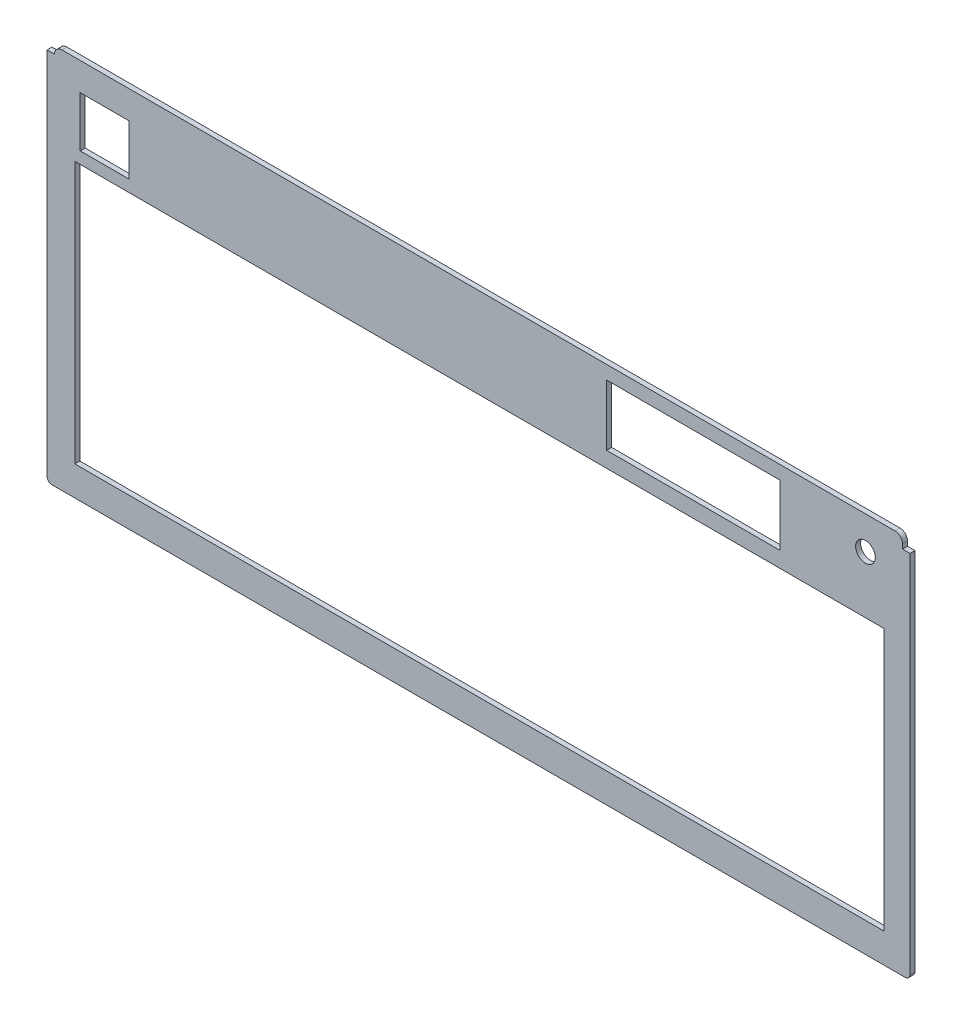
SolidWorks part; units mm, degrees
ref_plane "Front Plane" through (0, 0, 0) normal (0, 0, 1) x (1, 0, 0)
ref_plane "Top Plane" through (0, 0, 0) normal (0, 1, 0) x (1, 0, 0)
ref_plane "Right Plane" through (0, 0, 0) normal (1, 0, 0) x (0, 0, -1)
sketch "Sketch1" plane through (0, 0, 0) normal (0, 0, 1) x (1, 0, 0)
  line L0 (-65.3452, 80.1382) -> (268.63, 80.1382)
  line L6 (268.63, -69.8367) -> (-65.3452, -69.8367)
  line L7 (-68.3452, -66.8367) -> (-68.3452, 77.1382)
  line L10 (271.63, -66.8367) -> (271.63, 77.1382)
  line L12 (153.0356, 74.6937) -> (153.0356, 50.3137)
  line L13 (-58.0282, 68.9533) -> (-38.5345, 68.9533)
  line L14 (-58.0282, 68.9533) -> (-58.0282, 48.7377)
  line L15 (-58.0282, 48.7377) -> (-38.5345, 48.7377)
  line L16 (-38.5345, 68.9533) -> (-38.5345, 48.7377)
  line L17 (-60.1941, 44.0447) -> (264.3023, 44.0447)
  line L18 (-60.1941, 44.0447) -> (-60.1941, -61.0045)
  line L19 (-60.1941, -61.0045) -> (264.3023, -61.0045)
  line L20 (264.3023, 44.0447) -> (264.3023, -61.0045)
  line L25 (153.0356, 50.3137) -> (222.4656, 50.3137)
  line L26 (153.0356, 50.3137) -> (222.4656, 50.3137) construction
  line L27 (222.4656, 50.3137) -> (222.4656, 74.6937)
  line L28 (222.4656, 74.6937) -> (153.0356, 74.6937)
  arc A0 (-68.3452, 77.1382) -> (-65.3452, 80.1382) centre (-65.3452, 77.1382) cw
  arc A1 (268.63, 80.1382) -> (271.63, 77.1382) centre (268.63, 77.1382) cw
  arc A2 (268.63, -69.8367) -> (271.63, -66.8367) centre (268.63, -66.8367) ccw
  arc A3 (-65.3452, -69.8367) -> (-68.3452, -66.8367) centre (-65.3452, -66.8367) cw
  circle A4 centre (256.7754, 66.9302) radius 3.9489
  dimension "D1" = 3
  dimension "D2" = 3
extrude "Boss-Extrude1" add sketch "Sketch1" along normal blind 2
sketch "Sketch2" plane through (0, 0, 2) normal (0, 0, 1) x (1, 0, 0)
  line L0 (-68.3452, 77.1382) -> (-71.3373, 77.1382)
  line L1 (-71.3373, 77.1382) -> (-71.3373, -70.8494)
  line L2 (-69.3373, -72.8494) -> (272.6427, -72.8494)
  line L3 (274.6427, -70.8494) -> (274.6427, 75.3102)
  line L4 (274.6427, 75.3102) -> (271.6427, 75.3102)
  line L5 (271.6427, 75.3102) -> (271.6427, 77.1382) construction
  line L6 (274.6427, 75.3102) -> (271.6427, 75.3102) construction
  line L15 (-68.1452, 77.1382) -> (-68.1452, -66.8367)
  line L16 (-65.3452, -69.6367) -> (268.6303, -69.6367)
  line L17 (271.4303, -66.8369) -> (271.4427, 75.3102)
  line L18 (271.4427, 75.3102) -> (271.6427, 75.3102)
  line L20 (-68.3452, 77.1382) -> (-68.1452, 77.1382)
  arc A2 (-71.3373, -70.8494) -> (-69.3373, -72.8494) centre (-69.3373, -70.8494) ccw
  arc A3 (272.6427, -72.8494) -> (274.6427, -70.8494) centre (272.6427, -70.8494) ccw
  arc A4 (-68.1452, -66.8367) -> (-65.3452, -69.6367) centre (-65.3452, -66.8367) ccw
  arc A5 (268.6303, -69.6367) -> (271.4303, -66.8369) centre (268.6303, -66.8367) ccw
  dimension "D2" = 2
extrude "Boss-Extrude4" add sketch "Sketch2" against normal up to surface (2 mm away)
